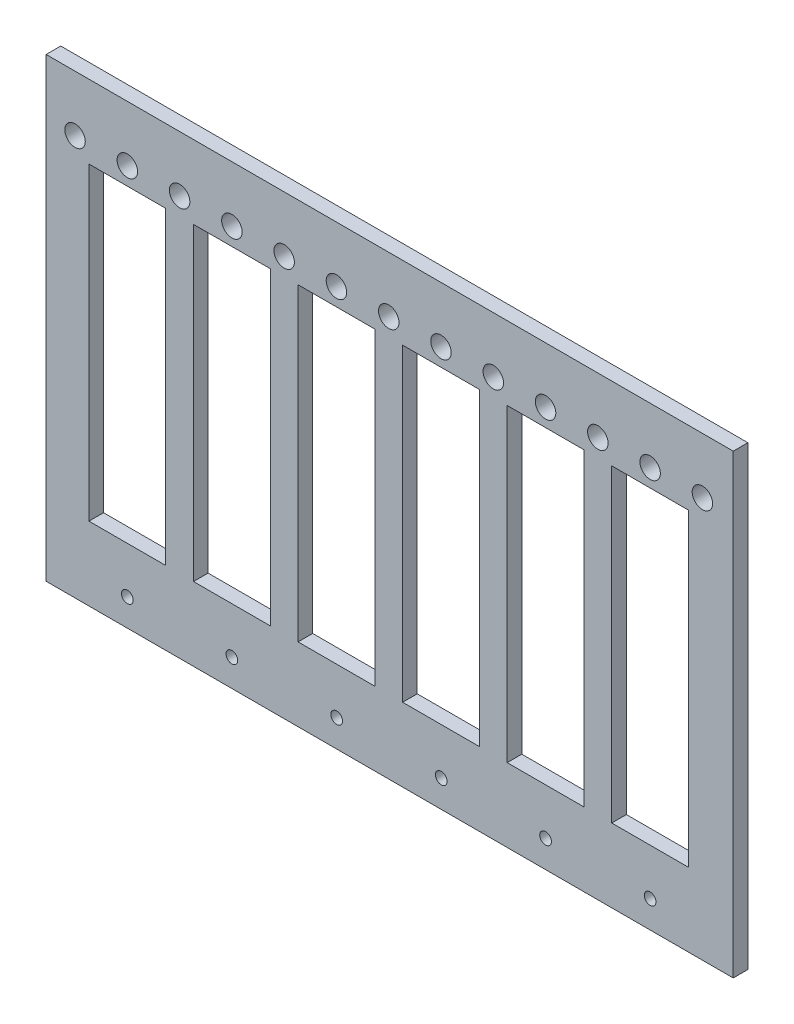
SolidWorks part; units mm, degrees
ref_plane "Front Plane" through (0, 0, 0) normal (0, 0, 1) x (1, 0, 0)
ref_plane "Top Plane" through (0, 0, 0) normal (0, 1, 0) x (1, 0, 0)
ref_plane "Right Plane" through (0, 0, 0) normal (1, 0, 0) x (0, 0, -1)
sketch "Sketch1" plane through (0, 0, 0) normal (0, 0, 1) x (1, 0, 0)
  line L0 (34.25, 211.5) -> (34.25, 251.5) construction
  line L1 (0, 0) -> (426, 0) construction
  line L2 (0, 0) -> (0, 211.5) construction
  line L3 (0, 211.5) -> (426, 211.5) construction
  line L4 (426, 0) -> (426, 211.5) construction
  line L5 (-21.27, -50.25) -> (448.59, -50.25)
  line L6 (0, 211.5) -> (0, 0) construction
  line L7 (105.75, 211.5) -> (105.75, 251.5) construction
  line L8 (8, 211.5) -> (8, 0) construction
  line L9 (448.59, -50.25) -> (448.59, 261.75)
  line L10 (60.5, 211.5) -> (60.5, 0) construction
  line L11 (177.25, 211.5) -> (177.25, 251.5) construction
  line L12 (79.5, 211.5) -> (79.5, 0) construction
  line L13 (8, 211.5) -> (60.5, 211.5)
  line L14 (426, 211.5) -> (426, 0) construction
  line L15 (8, 211.5) -> (8, 0)
  line L16 (418, 211.5) -> (418, 0) construction
  line L17 (132, 211.5) -> (132, 0) construction
  line L18 (8, 0) -> (60.5, 0)
  line L19 (151, 211.5) -> (151, 0) construction
  line L20 (60.5, 211.5) -> (60.5, 0)
  line L21 (203.5, 211.5) -> (203.5, 0) construction
  line L22 (79.5, 0) -> (132, 0)
  line L23 (222.5, 211.5) -> (222.5, 0) construction
  line L24 (79.5, 0) -> (79.5, 211.5)
  line L25 (275, 211.5) -> (275, 0) construction
  line L26 (79.5, 211.5) -> (132, 211.5)
  line L27 (294, 211.5) -> (294, 0) construction
  line L28 (132, 0) -> (132, 211.5)
  line L29 (346.5, 211.5) -> (346.5, 0) construction
  line L30 (151, 211.5) -> (203.5, 211.5)
  line L31 (365.5, 211.5) -> (365.5, 0) construction
  line L32 (151, 211.5) -> (151, 0)
  line L33 (0, 0) -> (426, 0) construction
  line L34 (0, 0) -> (0, -40) construction
  line L35 (0, -40) -> (426, -40) construction
  line L36 (426, 0) -> (426, -40) construction
  line L37 (0, 211.5) -> (426, 211.5) construction
  line L38 (0, 211.5) -> (0, 251.5) construction
  line L39 (0, 251.5) -> (426, 251.5) construction
  line L40 (426, 211.5) -> (426, 251.5) construction
  line L41 (151, 0) -> (203.5, 0)
  line L42 (203.5, 211.5) -> (203.5, 0)
  line L43 (222.5, 0) -> (275, 0)
  line L44 (222.5, 0) -> (222.5, 211.5)
  line L45 (222.5, 211.5) -> (275, 211.5)
  line L46 (275, 0) -> (275, 211.5)
  line L47 (294, 211.5) -> (346.5, 211.5)
  line L48 (294, 211.5) -> (294, 0)
  line L49 (294, 0) -> (346.5, 0)
  line L50 (346.5, 211.5) -> (346.5, 0)
  line L51 (365.5, 0) -> (418, 0)
  line L52 (365.5, 0) -> (365.5, 211.5)
  line L53 (365.5, 211.5) -> (418, 211.5)
  line L54 (418, 0) -> (418, 211.5)
  line L55 (-21.27, -50.25) -> (-21.27, 261.75)
  line L56 (248.75, 211.5) -> (248.75, 251.5) construction
  line L57 (320.25, 211.5) -> (320.25, 251.5) construction
  line L58 (391.75, 211.5) -> (391.75, 251.5) construction
  line L59 (-21.27, 261.75) -> (448.59, 261.75)
  line L60 (0, 223.5764) -> (426, 223.5764) construction
  line L61 (0, -31.6934) -> (426, -31.6934) construction
  line L62 (34.25, 0) -> (34.25, -40) construction
  line L63 (320.25, 0) -> (320.25, -40) construction
  line L64 (105.75, 0) -> (105.75, -40) construction
  line L65 (391.75, 0) -> (391.75, -40) construction
  line L66 (177.25, 0) -> (177.25, -40) construction
  line L68 (248.75, 0) -> (248.75, -40) construction
  circle A0 centre (391.75, 223.5764) radius 7
  circle A1 centre (320.25, 223.5764) radius 7
  circle A2 centre (248.75, 223.5764) radius 7
  circle A3 centre (177.25, 223.5764) radius 7
  circle A4 centre (105.75, 223.5764) radius 7
  circle A5 centre (34.25, 223.5764) radius 7
  circle A6 centre (34.25, -31.6934) radius 4
  circle A7 centre (105.75, -31.6934) radius 4
  circle A8 centre (177.4164, -31.6934) radius 4
  circle A9 centre (248.9164, -31.6934) radius 4
  circle A10 centre (320.25, -31.6934) radius 4
  circle A11 centre (391.75, -31.6934) radius 4
  circle A12 centre (70, 223.5764) radius 7
  circle A13 centre (105.75, 223.5764) radius 7 [skipped]
  circle A14 centre (141.5, 223.5764) radius 7
  circle A15 centre (177.25, 223.5764) radius 7 [skipped]
  circle A16 centre (213, 223.5764) radius 7
  circle A17 centre (248.75, 223.5764) radius 7 [skipped]
  circle A18 centre (284.5, 223.5764) radius 7
  circle A19 centre (320.25, 223.5764) radius 7 [skipped]
  circle A20 centre (356, 223.5764) radius 7
  circle A21 centre (391.75, 223.5764) radius 7 [skipped]
  circle A22 centre (427.5, 223.5764) radius 7
  circle A23 centre (-1.5, 223.5764) radius 7
  dimension "D2" = 12
  dimension "D1" = 5
  dimension "D3" = 2
extrude "Boss-Extrude1" add sketch "Sketch1" along normal blind 10
sketch "Sketch4" [suppressed] plane through (0, 0, 10) normal (0, 0, -1) x (-1, 0, 0)
  line L0 (-391.75, 211.5) -> (-391.75, 0) construction
  line L1 (-426, 183.75) -> (0, 183.75) construction
  line L2 (-320.25, 211.5) -> (-320.25, 0) construction
  line L3 (0, 26.25) -> (-426, 26.25) construction
  line L4 (-248.75, 211.5) -> (-248.75, 0) construction
  line L5 (-177.25, 211.5) -> (-177.25, 0) construction
  line L6 (-105.75, 211.5) -> (-105.75, 0) construction
  line L7 (-34.25, 211.5) -> (-34.25, 0) construction
  line L8 (-426, 131.25) -> (0, 131.25) construction
  line L10 (0, 78.75) -> (-426, 78.75) construction
  circle A0 centre (-391.75, 26.25) radius 1.5
  circle A1 centre (-320.25, 26.25) radius 1.5
  circle A2 centre (-248.75, 26.25) radius 1.5
  circle A3 centre (-177.25, 26.25) radius 1.5
  circle A4 centre (-105.75, 26.25) radius 1.5
  circle A5 centre (-34.25, 26.25) radius 1.5
  circle A6 centre (-320.25, 78.75) radius 1.5
  circle A7 centre (-248.75, 78.75) radius 1.5
  circle A8 centre (-177.25, 78.75) radius 1.5
  circle A9 centre (-105.75, 78.75) radius 1.5
  circle A10 centre (-34.25, 78.75) radius 1.5
  circle A11 centre (-320.25, 131.25) radius 1.5
  circle A12 centre (-248.75, 131.25) radius 1.5
  circle A13 centre (-177.25, 131.25) radius 1.5
  circle A14 centre (-105.75, 131.25) radius 1.5
  circle A15 centre (-34.25, 131.25) radius 1.5
  circle A16 centre (-320.25, 183.75) radius 1.5
  circle A17 centre (-248.75, 183.75) radius 1.5
  circle A18 centre (-177.25, 183.75) radius 1.5
  circle A19 centre (-105.75, 183.75) radius 1.5
  circle A20 centre (-34.25, 183.75) radius 1.5
  circle A21 centre (-391.75, 78.75) radius 1.5
  circle A22 centre (-391.75, 131.25) radius 1.5
  circle A23 centre (-391.75, 183.75) radius 1.5
  dimension "D2" = 6
  dimension "D1" = 6
  dimension "D3" = 4
